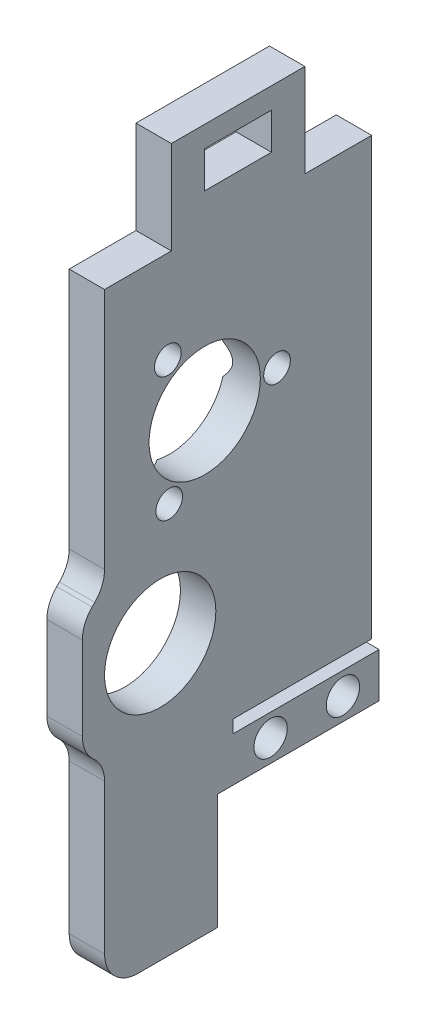
SolidWorks part; units mm, degrees
note: The reader was unsure of these and kept them because the rebuilt part matched: shared geometry of "Sketch2<4>".
ref_plane "Front Plane" through (0, 0, 0) normal (0, 0, 1) x (1, 0, 0)
ref_plane "Top Plane" through (0, 0, 0) normal (0, 1, 0) x (1, 0, 0)
ref_plane "Right Plane" through (0, 0, 0) normal (1, 0, 0) x (0, 0, -1)
sketch "Sketch2" plane through (0, 0, 0) normal (1, 0, 0) x (0, 0, -1)
  line L0 (0, 54.73) -> (24, 54.73)
  line L1 (24, 54.73) -> (24, 15.53)
  line L2 (10.17, 0) -> (0, 0)
  line L3 (-2, 19.7) -> (-2, 29.7)
  line L4 (-14.1477, -4) -> (43.3175, -4) construction
  line L14 (0, 31.7) -> (0, 54.73)
  line L16 (0, 17.7) -> (0, 0)
  line L19 (10.17, 0) -> (10.17, 10.38)
  line L20 (10.17, 10.38) -> (24.67, 10.38)
  line L25 (-2, 29.7) -> (0, 31.7)
  line L26 (-2, 19.7) -> (0, 17.7)
  line L28 (5, 29.7) -> (-2, 29.7) construction
  line L29 (5, 19.7) -> (-2, 19.7) construction
  line L31 (11.52, 15.53) -> (11.52, 14.38)
  line L40 (24.67, 14.38) -> (24.67, 10.38)
  line L41 (24.67, 14.38) -> (11.52, 14.38)
  line L42 (11.52, 15.53) -> (24, 15.53)
  circle A1 centre (5, 24.7) radius 5
  circle A2 centre (9, 40.8109) radius 8 construction
  circle A3 centre (9, 40.8109) radius 5
  dimension "D1" = 28.7
  dimension "D2" = 4
  dimension "D4" = 24
  dimension "D6" = 16
  dimension "D7" = 10
  dimension "D3" = 10
  dimension "D10" = 2
  dimension "D9" = 2
  dimension "D11" = 1.15
  dimension "D5" = 16.6
  dimension "D8" = 9
  dimension "D12" = 10.38
  dimension "D13" = 4
  dimension "D14" = 13.15
  dimension "D15" = 1.35
  dimension "D16" = 10.17
  dimension "D17" = 39.2
extrude "Boss-Extrude1" add sketch "Sketch2" against normal blind 3.18 contours L0 L1 L42 L31 L41 L40 L20 L19 L2 L16 L26 L3 L25 L14
extrude "Cut-Extrude2" cut sketch "Sketch2<4>" against normal blind 3.18 flip side to cut
sketch "Sketch2<4>" plane through (0, 0, 0) normal (1, 0, 0) x (0, 0, -1) same geometry as "Sketch2"
fillet "Fillet6" radius 3 5 edges at (-1.59, 17.7, 0) (-1.59, 19.7, 2) (-1.59, 29.7, 2) (-1.59, 31.7, 0) (-1.59, 0, 0)
sketch "Sketch10" plane through (-3.18, 0, 0) normal (-1, 0, 0) x (0, 0, 1)
  line L0 (-15.4996, 40.8823) -> (-5.6884, 46.404) construction
  line L1 (-5.6884, 46.404) -> (-5.812, 35.1463) construction
  line L2 (-5.812, 35.1463) -> (-15.4996, 40.8823) construction
  circle A0 centre (-9, 40.8109) radius 6.5 construction
  circle A1 centre (-5.6884, 46.404) radius 1
  circle A2 centre (-5.812, 35.1463) radius 1
  circle A3 centre (-15.4996, 40.8823) radius 1
  dimension "D1" = 13
  dimension "D2" = 2
hole_wizard "M2x0.4 Tapped Hole1" [suppressed] positions "Sketch5" profile "Sketch6" tap size "M2x0.4" standard "ANSI Metric"
sketch "Sketch5" plane through (0, 54.29, 0) normal (0, 1, 0) x (1, 0, 0)
  line L0 (-3.18, 24) -> (0, 24) construction
  line L1 (-3.18, 0) -> (0, 0) construction
  line L2 (0, 0) -> (0, 24) construction
  point P0 (-1.59, 21.5)
  point P2 (-1.59, 2.5)
  point P13 (-1.59, 21.5)
  dimension "D1" = 2.5
  dimension "D2" = 2.5
  dimension "D3" = 1.59
sketch "Sketch6" plane through (-1.59, 54.29, -21.5) normal (1, 0, 0) x (0, 0, 1)
  line L0 (0, 0) -> (0, 6)
  line L1 (0, 6) -> (0.8, 5.5193)
  line L2 (0.8, 5.5193) -> (0.8, 0)
  line L5 (0.8, 0) -> (0, 0)
  line L10 (0, 6) -> (-0.8, 5.5193) construction
  line L11 (0, -6.35) -> (0, 107.95) construction
  dimension "Tap Drill Dia." = 1.6
  dimension "Tap Drill Depth" = 6
  dimension "Drill Angle" = 118
hole_wizard "CSK for M2 Flat Head Machine Screw2" positions "Sketch11" profile "Sketch12" countersink size "M2" standard "ANSI Metric" end condition up to next
sketch "Sketch11" plane through (-3.18, 0, 0) normal (-1, 0, 0) x (0, 0, 1)
  point P0 (-5.6884, 46.404)
  point P3 (-15.4996, 40.8823)
  point P6 (-5.812, 35.1463)
sketch "Sketch12" plane through (-3.18, 46.404, -5.6884) normal (0, 1, 0) x (0, 0, 1)
  line L0 (0, 0) -> (0, 3.18)
  line L1 (0, 3.18) -> (1.2, 3.18)
  line L2 (1.2, 3.18) -> (1.2, 1)
  line L3 (1.2, 1) -> (2.2, 0)
  line L5 (2.2, 0) -> (0, 0)
  line L6 (-1.2, 1) -> (-2.2, 0) construction
  line L11 (0, -6.35) -> (0, 107.95) construction
  dimension "Thru Hole Dia." = 2.4
  dimension "Thru Hole Depth" = 3.18
  dimension "Near C'Sink Dia." = 4.4
  dimension "Near C'Sink Angle" = 90
mirror "Mirror1" [suppressed]
delete or keep bodies "Body-Delete/Keep 1" [suppressed] type delete bodies bodies 104
hole_wizard "M3x0.5 Tapped Hole1" positions "Sketch13" profile "Sketch15" tap size "M3x0.5" standard "ANSI Metric"
sketch "Sketch13" plane through (0, 0, 0) normal (1, 0, 0) x (0, 0, -1)
  line L0 (24.67, 14.38) -> (24.67, 10.38) construction
  line L1 (24.67, 14.38) -> (11.52, 14.38) construction
  point P2 (21.42, 12.38)
  point P4 (14.92, 12.38)
  dimension "D1" = 3.25
  dimension "D2" = 6.5
  dimension "D3" = 2
sketch "Sketch15" plane through (0, 12.38, -21.42) normal (0, 1, 0) x (0, 0, -1)
  line L0 (0, 0) -> (0, 4.23)
  line L1 (0, 4.23) -> (1.5, 3.3287)
  line L2 (1.5, 3.3287) -> (1.5, 0)
  line L5 (1.5, 0) -> (0, 0)
  line L10 (0, 4.23) -> (-1.5, 3.3287) construction
  line L11 (0, -6.35) -> (0, 107.95) construction
  dimension "Tap Drill Dia." = 3
  dimension "Tap Drill Depth" = 4.23
  dimension "Drill Angle" = 118
cosmetic thread "Hole Thread1" parameters "D1"=1.73, "D2"=3
cosmetic thread "Hole Thread2" parameters "D1"=1.73, "D2"=3
sketch "Sketch16" plane through (0, 54.73, 0) normal (0, 1, 0) x (1, 0, 0)
  line L0 (-3.18, 24) -> (0, 0) construction
  line L1 (0, 0) -> (0, 24) construction
  line L2 (-3.18, 18) -> (0, 18)
  line L3 (-3.18, 18) -> (-3.18, 6)
  line L4 (-3.18, 6) -> (0, 6)
  line L5 (0, 18) -> (0, 6)
  line L6 (-3.18, 18) -> (0, 6) construction
  line L7 (-3.18, 6) -> (0, 18) construction
  point P4 (-1.59, 12)
  dimension "D1" = 12
extrude "Boss-Extrude2" add sketch "Sketch16" along normal blind 8.36
sketch "Sketch18" plane through (0, 0, 0) normal (1, 0, 0) x (0, 0, -1)
  line L0 (6, 54.73) -> (18, 54.73) construction
  line L2 (9, 61.19) -> (15, 61.19)
  line L3 (9, 61.19) -> (9, 57.91)
  line L4 (9, 57.91) -> (15, 57.91)
  line L5 (15, 61.19) -> (15, 57.91)
  line L6 (9, 61.19) -> (15, 57.91) construction
  line L7 (9, 57.91) -> (15, 61.19) construction
  point P4 (12, 59.55)
  point P10 (12, 54.73)
  dimension "D1" = 3.28
  dimension "D2" = 6
  dimension "D3" = 3.18
extrude "Cut-Extrude3" cut sketch "Sketch18" against normal through all
equation "\"RollerToBaseplate\"= 28.7mm"
equation "\"SteelShaftDia\"= 10mm"
equation "\"DribblerMotorDia\"= 16mm"
equation "\"DribblerHeight\"= 50mm"
equation "\"Width\"= 24"
equation "\"MaterialThickness\"= 3.18mm"
equation "\"D1@Sketch16\"=\"Width\"/2"
equation "\"D1@Boss-Extrude2\"=\"MaterialThickness\"*2 +2mm"
equation "\"D1@Sketch18\"=\"MaterialThickness\"+0.1mm"
equation "\"D2@Sketch18\"=\"Width\"/4"
equation "\"D3@Sketch18\"=\"MaterialThickness\""
